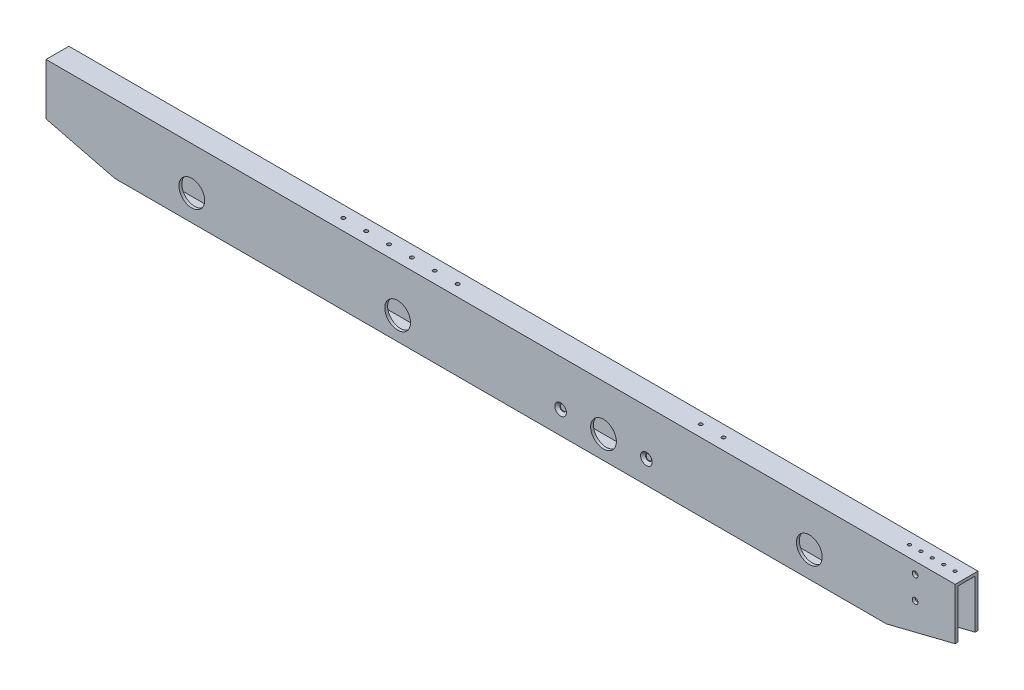
SolidWorks part; units mm, degrees
material "6061-T6 (SS)"
ref_plane "Front Plane" through (0, 0, 0) normal (0, 0, 1) x (1, 0, 0)
ref_plane "Top Plane" through (0, 0, 0) normal (0, 1, 0) x (1, 0, 0)
ref_plane "Right Plane" through (0, 0, 0) normal (1, 0, 0) x (0, 0, -1)
sketch "Sketch1" plane through (0, 0, 0) normal (0, 0, 1) x (1, 0, 0)
  line L0 (0, -12.7) -> (-342.9, -9.525) construction
  line L1 (-504.825, 38.1) -> (504.825, 38.1)
  line L2 (-504.825, 38.1) -> (-504.825, -38.1)
  line L3 (-504.825, -38.1) -> (504.825, -38.1)
  line L4 (504.825, 38.1) -> (504.825, -38.1)
  line L5 (-504.825, 38.1) -> (504.825, -38.1) construction
  line L6 (-504.825, -38.1) -> (504.825, 38.1) construction
  line L7 (-504.825, -38.1) -> (504.825, -38.1) construction
  line L8 (-504.825, -38.1) -> (-504.825, 12.7) construction
  line L9 (-339.7523, -73.025) -> (358.7477, -73.025) construction
  line L10 (-504.825, 12.7) -> (504.825, 12.7) construction
  line L11 (504.825, -38.1) -> (504.825, 12.7) construction
  line L12 (0, -12.7) -> (342.9, -9.525) construction
  line L13 (-114.3, -12.7) -> (114.3, -12.7) construction
  circle A0 centre (-114.3, -12.7) radius 14.2875
  circle A1 centre (114.3, -12.7) radius 14.2875
  circle A2 centre (-342.9, -9.525) radius 14.2875
  circle A3 centre (342.9, -9.525) radius 14.2875
  circle A4 centre (-342.9, -9.525) radius 63.5 construction
  circle A5 centre (-114.3, -12.7) radius 63.5 construction
  circle A6 centre (114.3, -12.7) radius 63.5 construction
  circle A7 centre (342.9, -9.525) radius 63.5 construction
  point P0 (0, 0)
  point P12 (0, -38.1)
  dimension "D5" = 228.6
  dimension "D4" = 50.8
  dimension "D8" = 228.6
  dimension "D9" = 28.575
  dimension "D6" = 28.575
  dimension "D10" = 127
  dimension "D1" = 76.2
  dimension "D2" = 1009.65
  dimension "D3" = 25.4
  dimension "D7" = 228.6
extrude "Boss-Extrude2" add sketch "Sketch1" along normal mid plane 25.4
sketch "Sketch3" plane through (504.825, 0, 0) normal (1, 0, 0) x (0, 0, -1)
  line L8 (9.525, -34.925) -> (9.525, 34.925)
  line L9 (9.525, 34.925) -> (-9.525, 34.925)
  line L10 (-9.525, 34.925) -> (-9.525, -34.925)
  line L11 (-9.525, -34.925) -> (9.525, -34.925)
  line L12 (9.525, -34.925) -> (9.525, 34.925)
  line L13 (9.525, 34.925) -> (-9.525, 34.925)
  line L14 (-9.525, 34.925) -> (-9.525, -34.925)
  line L15 (-9.525, -34.925) -> (9.525, -34.925)
  dimension "D1" = 3.175
extrude "Cut-Extrude2" cut sketch "Sketch3" against normal through all
sketch "Sketch4" plane through (0, 0, 12.7) normal (0, 0, 1) x (1, 0, 0)
  line L0 (-504.825, -38.1) -> (-504.825, -19.05)
  line L1 (-504.825, 38.1) -> (-504.825, -38.1) construction
  line L2 (-504.825, -19.05) -> (-428.625, -38.1)
  line L3 (-504.825, -38.1) -> (504.825, -38.1) construction
  line L4 (-428.625, -38.1) -> (-504.825, -38.1)
  line L5 (0, -38.1) -> (0, 38.1) construction
  line L6 (504.825, 38.1) -> (-504.825, 38.1) construction
  line L7 (428.625, -38.1) -> (504.825, -38.1)
  line L8 (504.825, -38.1) -> (504.825, -19.05)
  line L9 (504.825, -19.05) -> (428.625, -38.1)
  line L11 (504.825, -19.05) -> (504.825, 38.1) construction
  point P15 (0, 0)
  dimension "D1" = 19.05
  dimension "D2" = 57.15
  dimension "D3" = 76.2
  dimension "D4" = 504.825
  dimension "D5" = 14.036
extrude "Cut-Extrude3" cut sketch "Sketch4" against normal through all
sketch "Sketch9" plane through (0, 38.1, 0) normal (0, 1, 0) x (1, 0, 0)
  line L0 (504.825, -12.7) -> (504.825, 12.7) construction
  circle A0 centre (492.125, 0) radius 1.7272
  circle A1 centre (479.425, 0) radius 1.7272
  circle A2 centre (466.725, 0) radius 1.7272
  circle A3 centre (454.025, 0) radius 1.7272
  circle A4 centre (441.325, 0) radius 1.7272
  point P2 (504.825, 0)
  dimension "D1" = 3.4544
  dimension "D2" = 12.7
  dimension "D3" = 4
  dimension "D4" = 2
extrude "Cut-Extrude4" cut sketch "Sketch9" against normal blind 2.54
sketch "Sketch12" plane through (0, 38.1, 0) normal (0, 1, 0) x (1, 0, 0)
  line L0 (-504.825, -12.7) -> (-504.825, 12.7) construction
  circle A0 centre (-187.325, 0) radius 2.0193
  circle A1 centre (-161.925, 0) radius 2.0193
  circle A2 centre (-136.525, 0) radius 2.0193
  circle A3 centre (-111.125, 0) radius 2.0193
  circle A4 centre (-85.725, 0) radius 2.0193
  circle A5 centre (-60.325, 0) radius 2.0193
  point P5 (-28.575, 0)
  point P15 (-504.825, 0)
  dimension "D1" = 4.0386
  dimension "D2" = 317.5
  dimension "D4" = 476.25
  dimension "D3" = 6
extrude "Cut-Extrude7" cut sketch "Sketch12" against normal blind 5.08
hole_wizard "CSK for 1/4 Flat Head Machine Screw (100)2" positions "Sketch16" profile "Sketch15" countersink size "1/4" standard "ANSI Inch" end condition through all
sketch "Sketch16" plane through (0, 0, 12.7) normal (0, 0, 1) x (1, 0, 0)
  circle A0 centre (114.3, -12.7) radius 14.2875 construction
  point P4 (66.675, -12.7)
  point P6 (161.925, -12.7)
  dimension "D1" = 47.625
  dimension "D2" = 47.625
sketch "Sketch15" plane through (66.675, -12.7, 12.7) normal (1, 0, 0) x (0, -1, 0)
  line L0 (0, 0) -> (0, 25.4)
  line L1 (0, 25.4) -> (3.3782, 25.4)
  line L2 (3.3782, 25.4) -> (3.3782, 2.5682)
  line L3 (3.3782, 2.5682) -> (6.4389, 0)
  line L5 (6.4389, 0) -> (0, 0)
  line L6 (-3.3782, 2.5682) -> (-6.4389, 0) construction
  line L11 (0, -6.35) -> (0, 107.95) construction
  dimension "Thru Hole Dia." = 6.7564
  dimension "Thru Hole Depth" = 25.4
  dimension "Near C'Sink Dia." = 12.8778
  dimension "Near C'Sink Angle" = 100
sketch "Sketch17" plane through (0, -38.1, 0) normal (0, -1, 0) x (-1, 0, 0)
  line L2 (504.825, 9.525) -> (504.825, -9.525) construction
  circle A0 centre (-396.875, 0) radius 1.7272
  circle A1 centre (-320.675, 0) radius 1.7272
  circle A2 centre (-244.475, 0) radius 1.7272
  circle A3 centre (-168.275, 0) radius 1.7272
  circle A4 centre (-92.075, 0) radius 1.7272
  circle A5 centre (-15.875, 0) radius 1.7272
  circle A6 centre (60.325, 0) radius 1.7272
  point P2 (504.825, 0)
  dimension "D1" = 3.4544
  dimension "D2" = 444.5
  dimension "D3" = 7
extrude "Cut-Extrude8" cut sketch "Sketch17" against normal blind 6.35
sketch "Sketch18" plane through (0, 0, -12.7) normal (0, 0, -1) x (-1, 0, 0)
  circle A0 centre (-114.3, -12.7) radius 17.4625
  dimension "D1" = 34.925
extrude "Cut-Extrude9" cut sketch "Sketch18" against normal blind 3.81
hole_wizard "1/4 (0.25) Diameter Hole1" positions "Sketch20" profile "Sketch19" hole size "1/4" standard "ANSI Inch" end condition through all
sketch "Sketch20" plane through (0, 0, 12.7) normal (0, 0, 1) x (1, 0, 0)
  line L0 (504.825, -19.05) -> (504.825, 38.1) construction
  line L1 (504.825, 38.1) -> (-504.825, 38.1) construction
  point P0 (460.375, 25.4)
  point P2 (460.375, 0)
  dimension "D1" = 25.4
  dimension "D2" = 44.45
  dimension "D3" = 12.7
sketch "Sketch19" plane through (460.375, 25.4, 12.7) normal (1, 0, 0) x (0, -1, 0)
  line L0 (0, 0) -> (0, 25.4)
  line L1 (0, 25.4) -> (3.175, 25.4)
  line L2 (3.175, 25.4) -> (3.175, 0)
  line L5 (3.175, 0) -> (0, 0)
  line L11 (0, -6.35) -> (0, 107.95) construction
  dimension "Thru Hole Dia." = 6.35
  dimension "Thru Hole Depth" = 25.4
hole_wizard "#10-32 Tapped Hole2" positions "Sketch24" profile "Sketch23" tap size "#10-32" standard "ANSI Inch" end condition through all
sketch "Sketch24" plane through (0, 38.1, 0) normal (0, 1, 0) x (1, 0, 0)
  line L0 (504.825, -12.7) -> (504.825, 12.7) construction
  point P0 (234.95, 0)
  point P2 (209.55, 0)
  dimension "D1" = 269.875
  dimension "D2" = 25.4
sketch "Sketch23" plane through (234.95, 38.1, 0) normal (1, 0, 0) x (0, 0, 1)
  line L0 (0, 0) -> (0, 76.2)
  line L1 (0, 76.2) -> (2.0193, 76.2)
  line L2 (2.0193, 76.2) -> (2.0193, 0)
  line L5 (2.0193, 0) -> (0, 0)
  line L11 (0, -6.35) -> (0, 107.95) construction
  dimension "Thread Major Dia." = 4.0386
  dimension "Thru Tap Drill Depth" = 76.2
